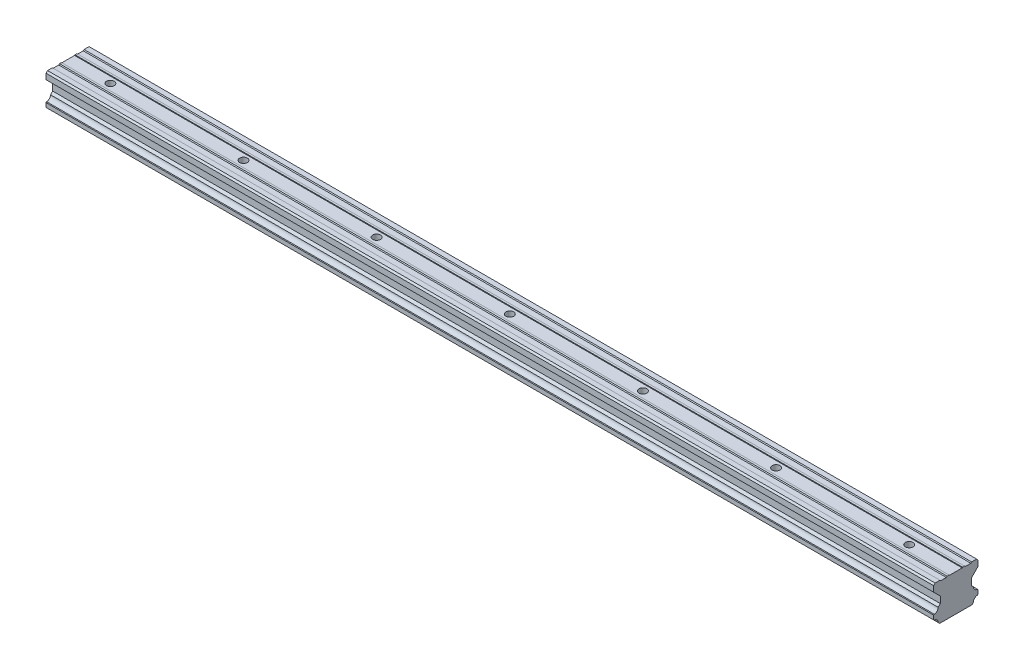
SolidWorks part; units mm, degrees
material "AISI 1020 Steel, Cold Rolled"
ref_plane "Front Plane" through (0, 0, 0) normal (0, 0, 1) x (1, 0, 0)
ref_plane "Top Plane" through (0, 0, 0) normal (0, 1, 0) x (1, 0, 0)
ref_plane "Right Plane" through (0, 0, 0) normal (1, 0, 0) x (0, 0, -1)
sketch "Sketch1" plane through (0, 0, 0) normal (1, 0, 0) x (0, 0, -1)
  line L0 (-7.9658, -7.694) -> (-7.2663, -8.3935)
  line L1 (-7.2663, -8.3935) -> (7.2663, -8.3935)
  line L2 (7.2663, -8.3935) -> (7.9658, -7.694)
  line L3 (9.7474, -5.9133) -> (10, -5.6608)
  line L4 (10, -5.6608) -> (10, -3.7884)
  line L5 (10, -3.7884) -> (9.7474, -3.5358)
  line L6 (7.9658, -1.7232) -> (7.0051, -0.7626)
  line L7 (7.0051, -0.7626) -> (7.0051, 2.1662)
  line L8 (7.0051, 2.1662) -> (10, 5.1611)
  line L9 (10, 5.1611) -> (10, 7.7124)
  line L10 (10, 7.7124) -> (9.4085, 8.3935)
  line L11 (9.4085, 8.3935) -> (7.133, 8.3935)
  line L12 (7.133, 8.3935) -> (6.7895, 8.05)
  line L13 (6.7895, 8.05) -> (4.2711, 8.05)
  line L14 (4.2711, 8.05) -> (3.9277, 8.3935)
  line L15 (3.9277, 8.3935) -> (3.0613, 8.3935)
  line L16 (3.0613, 8.3935) -> (2.872, 8.2042)
  line L17 (2.872, 8.2042) -> (-2.872, 8.2042)
  line L18 (-2.872, 8.2042) -> (-3.0613, 8.3935)
  line L19 (-3.0613, 8.3935) -> (-3.9277, 8.3935)
  line L20 (-3.9277, 8.3935) -> (-4.2712, 8.05)
  line L21 (-4.2712, 8.05) -> (-6.7895, 8.05)
  line L22 (-6.7895, 8.05) -> (-7.133, 8.3935)
  line L23 (-7.133, 8.3935) -> (-9.3077, 8.3935)
  line L24 (-9.3077, 8.3935) -> (-10, 7.7012)
  line L25 (-10, 7.7012) -> (-10, 5.1611)
  line L26 (-10, 5.1611) -> (-7.0051, 2.1662)
  line L27 (-7.0051, 2.1662) -> (-7.0051, -0.7626)
  line L28 (-7.0051, -0.7626) -> (-7.9658, -1.7232)
  line L29 (-9.7474, -5.9133) -> (-10, -5.6608)
  line L30 (-10, -5.6608) -> (-10, -3.7884)
  line L31 (-10, -3.7884) -> (-9.7474, -3.5358)
  arc A0 (-7.9658, -7.694) -> (-9.7474, -5.9133) centre (-9.7035, -7.6511) ccw
  arc A1 (-9.7474, -3.5358) -> (-7.9658, -1.7232) centre (-9.7025, -1.7981) ccw
  arc A2 (7.9658, -1.7232) -> (9.7474, -3.5358) centre (9.7025, -1.7981) ccw
  arc A3 (9.7474, -5.9133) -> (7.9658, -7.694) centre (9.7035, -7.6511) ccw
extrude "Boss-Extrude1" add sketch "Sketch1" along normal blind 400
sketch "Sketch2" plane through (0, -8.3935, 0) normal (0, -1, 0) x (1, 0, 0)
  circle A0 centre (19, 0) radius 3
  dimension "D1" = 6
  dimension "D2" = 19
hole_wizard "Hole1" positions "3DSketch1" profile "Sketch3" legacy end condition through all
sketch3d "3DSketch1"
  point P0 (19, -8.3935, 0)
sketch "Sketch3" plane through (19, -8.3935, 0) normal (1, 0, 0) x (0, 0, -1)
  line L0 (0, 0) -> (0, 16.7869)
  line L1 (0, 16.7869) -> (1.75, 16.7869)
  line L2 (1.75, 16.7869) -> (1.75, 8.5)
  line L3 (1.75, 8.5) -> (3, 8.5)
  line L4 (3, 8.5) -> (3, 0)
  line L5 (3, 0) -> (0, 0)
  line L6 (0, 110) -> (0, -10) construction
  dimension "Diameter" = 3.5
  dimension "Depth" = 16.7869
  dimension "C-Bore Diameter" = 6
  dimension "C-Bore Depth" = 8.5
sketch "Sketch4" plane through (0, -8.3935, 0) normal (0, -1, 0) x (-1, 0, 0)
  line L0 (0, 0) -> (-400, 0) construction
  line L1 (-400, -7.2663) -> (-400, 7.2663) construction
pattern_linear "LPattern1" count 7 spacing 60 along (1, 0, 0) of "Hole1"
